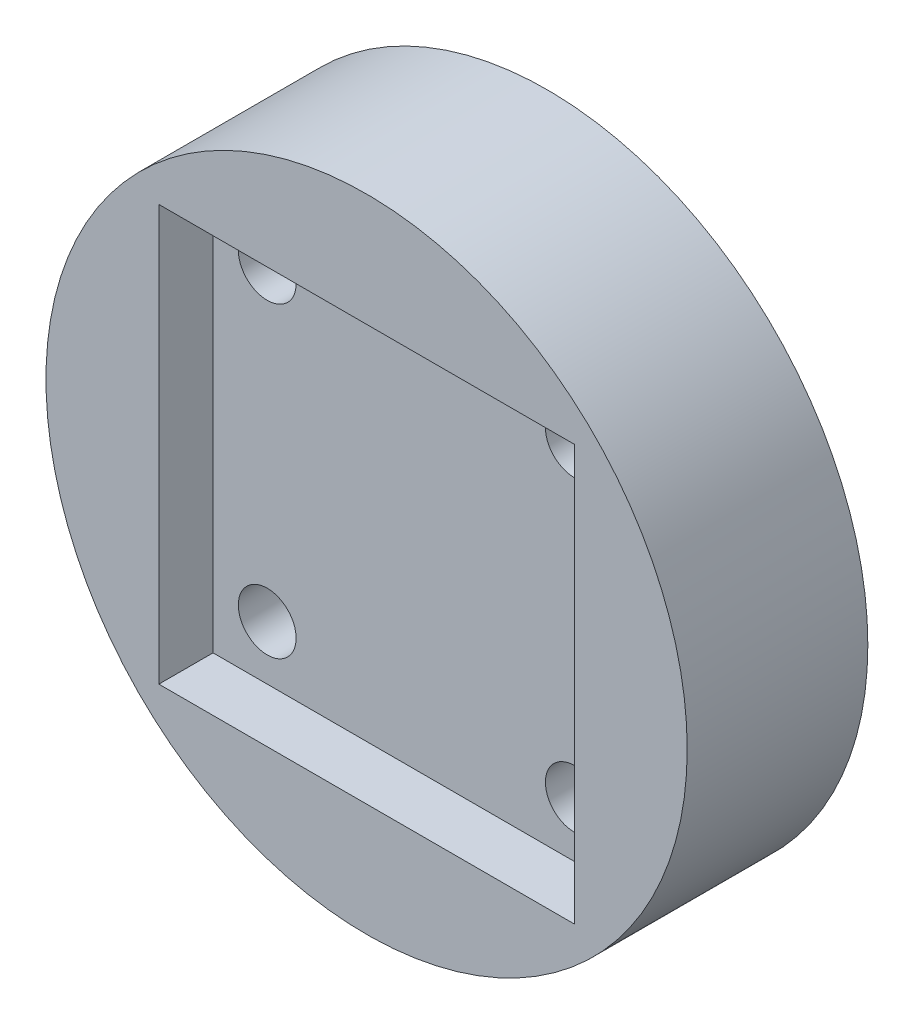
SolidWorks part; units mm, degrees
ref_plane "Front Plane" through (0, 0, 0) normal (1, 0, 0) x (0, 1, 0)
ref_plane "Top Plane" through (0, 0, 0) normal (0, 0, 1) x (0, 1, 0)
ref_plane "Right Plane" through (0, 0, 0) normal (0, 1, 0) x (-1, 0, 0)
sketch "Sketch1" plane through (0, 0, 0) normal (0, 0, 1) x (0, 1, 0)
  line L1 (-11.5, -11.5) -> (11.5, -11.5)
  line L2 (-11.5, -11.5) -> (-11.5, 11.5)
  line L3 (-11.5, 11.5) -> (11.5, 11.5)
  line L4 (11.5, -11.5) -> (11.5, 11.5)
  line L5 (-11.5, -11.5) -> (11.5, 11.5) construction
  line L6 (-11.5, 11.5) -> (11.5, -11.5) construction
  circle A0 centre (0, 0) radius 17.75
  circle A1 centre (-8.5, 8.5) radius 1.6
  circle A2 centre (8.5, 8.5) radius 1.6
  circle A3 centre (8.5, -8.5) radius 1.6
  circle A4 centre (-8.5, -8.5) radius 1.6
  point P0 (0, 0)
  dimension "D1" = 35.5
  dimension "D3" = 3.2
  dimension "D5" = 17
  dimension "D2" = 23
  dimension "D4" = 4
extrude "Boss-Extrude1" add sketch "Sketch1" along normal blind 10 contours L1 L4 L3 L2 A4 A3 A2 A1 | A4 | A3 | A1 | A2 | A0 L4 L1 L2 L3 region at (0, 0, 0) region at (0, -17.248, 0) region at (-8.5, -8.5, 0) region at (-8.5, 8.5, 0) region at (8.5, 8.5, 0) region at (8.5, -8.5, 0)
extrude "Cut-Extrude1" cut sketch "Sketch1<3>" against normal blind 3 from surface contours L1 L4 L3 L2 A4 A3 A2 A1 | A1 | A2 | A4 | A3 region at (0, 0, 0) region at (-8.5, -8.5, 0) region at (-8.5, 8.5, 0) region at (8.5, 8.5, 0) region at (8.5, -8.5, 0) starting at face at (17.75, 0, 10)
sketch "Sketch1<3>" plane through (0, 0, 0) normal (0, 0, 1) x (0, 1, 0) same geometry as "Sketch1"
extrude "Cut-Extrude3" cut sketch "Sketch1<4>" along normal through all contours A4 | A3 | A2 | A1 region at (-8.5, -8.5, 0) region at (-8.5, 8.5, 0) region at (8.5, 8.5, 0) region at (8.5, -8.5, 0)
sketch "Sketch1<4>" plane through (0, 0, 0) normal (0, 0, 1) x (0, 1, 0) same geometry as "Sketch1"
equation "\"AS5600Height\"= 3"
equation "\"D1@Cut-Extrude1\"=\"AS5600Height\""
